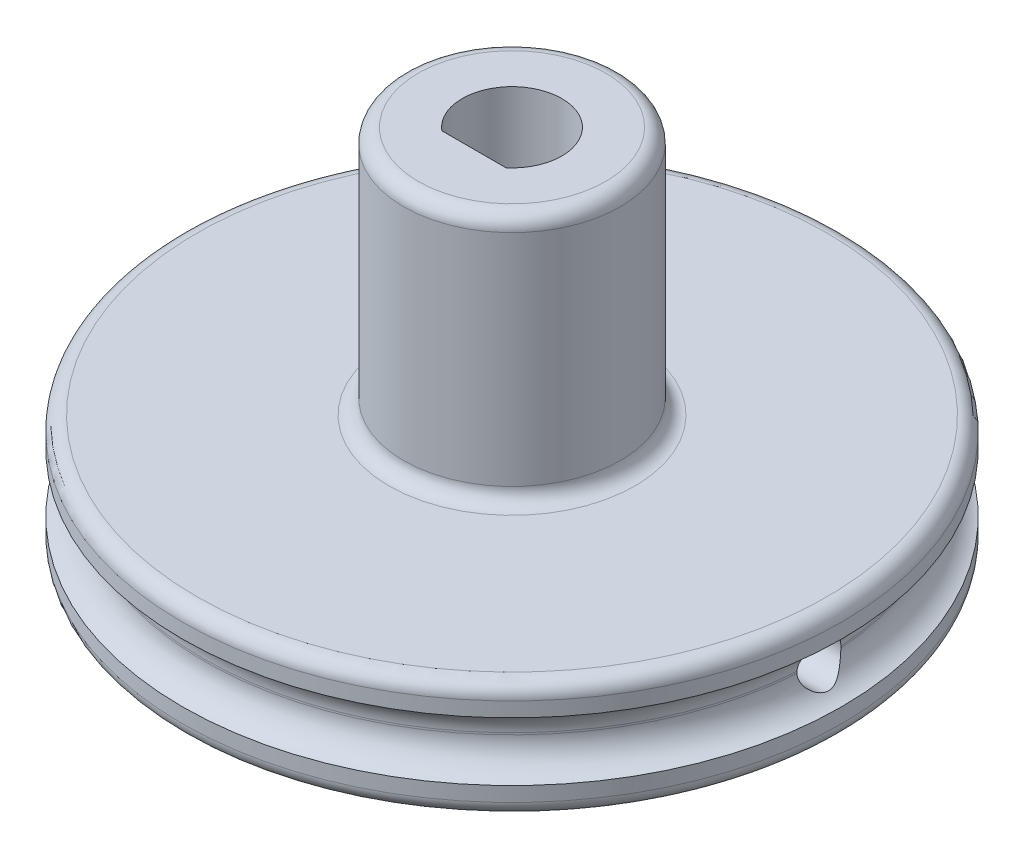
SolidWorks part; units mm, degrees
ref_plane "Front Plane" through (0, 0, 0) normal (0, 0, 1) x (1, 0, 0)
ref_plane "Top Plane" through (0, 0, 0) normal (0, 1, 0) x (1, 0, 0)
ref_plane "Right Plane" through (0, 0, 0) normal (1, 0, 0) x (0, 0, -1)
sketch "Sketch1" plane through (0, 0, 0) normal (0, 1, 0) x (1, 0, 0)
  line L0 (-1.0954, -1.3) -> (1.0954, -1.3)
  line L1 (0, -1.3) -> (0, -1.7)
  circle A0 centre (0, 0) radius 1.7
  circle A1 centre (0, 0) radius 11.25
  dimension "D1" = 3.4
  dimension "D2" = 22.5
  dimension "D3" = 0.4
extrude "Boss-Extrude1" add sketch "Sketch1" along normal blind 4 contours A1 A0 | L1 A0 L0 | L0 A0 L1 region at (-0.4181, 0, 1.4617) region at (0.4181, 0, 1.4617) region at (-10.9318, 0, 0)
sketch "Sketch2" plane through (0, 4, 0) normal (0, 1, 0) x (1, 0, 0)
  line L1 (1.7, 0) -> (3.7, 0) construction
  line L2 (-1.0954, -1.3) -> (1.0954, -1.3)
  circle A0 centre (0, 0) radius 3.7
  arc A1 (1.0954, -1.3) -> (-1.0954, -1.3) centre (0, 0) ccw construction
  arc A2 (-1.0954, -1.3) -> (1.0954, -1.3) centre (0, 0) cw
  dimension "D2" = 1.7
  dimension "D1" = 2
extrude "Boss-Extrude2" add sketch "Sketch2" along normal blind 8.5
sketch "Sketch3" plane through (0, 12.5, 0) normal (0, 1, 0) x (1, 0, 0)
  line L0 (0, 0) -> (0, -3.7) construction
  circle A0 centre (0, 0) radius 3.7 construction
sketch "Sketch4" plane through (0, 0, 0) normal (0, -1, 0) x (1, 0, 0)
  line L0 (0, 0) -> (0, 11.25) construction
  circle A0 centre (0, 0) radius 11.25 construction
ref_plane "Plane1" through (0, 0, 0) normal (1, 0, 0) x (0, 0, -1)
ref_plane "Plane2" through (12.5, 0, 0) normal (1, 0, 0) x (0, 0, -1)
sketch "Sketch5" plane through (12.5, 0, 0) normal (1, 0, 0) x (0, 0, -1)
  line L0 (0, 0) -> (0, 4) construction
  line L4 (11.25, 4) -> (-11.25, 4) construction
  circle A0 centre (0, 2) radius 0.75
  dimension "D1" = 1.5
sketch3d "3DSketch1"
  line L0 (12.5, 0, 0) -> (12.5, 4, 0) construction
  line L1 (12.5, 2, 0) -> (9.1368, 2, 0)
  line L3 (9.1368, 2, 0) -> (7.1368, 2, 0) construction
  line L4 (7.1368, 0, 0) -> (7.1368, -2.2816, 0)
  arc A0 (7.1368, 0, 0) -> (9.1368, 2, 0) centre (9.1368, 0, 0) ccw
  point P6 (7.1368, 2, 0)
  point P8 (9.1368, 0, -2)
  dimension "D1" = 2
sweep "Cut-Sweep1" cut path "3DSketch1" circular profile diameter 1.5 parameters "D3"=1.5
mirror "Mirror1" about plane through (0, 0, 0) normal (1, 0, 0) of "Cut-Sweep1"
ref_plane "Plane3" through (0, 2, 0) normal (0, 1, 0) x (1, 0, 0)
sketch "Sketch21" plane through (0, 2, 0) normal (0, 1, 0) x (1, 0, 0)
  circle A0 centre (0, 0) radius 12.5
  circle A1 centre (0, 0) radius 10.5
  dimension "D1" = 25
  dimension "D2" = 2
extrude "Cut-Extrude1" cut sketch "Sketch21" against normal mid plane 2
fillet "Fillet1" radius 1 2 edges at (0, 1, 10.5) (0, 3, 10.5)
fillet "Fillet2" radius 0.5 4 edges at (0, 4, 3.7) (0, 12.5, 3.7) (0, 0, 11.25) (0, 4, 11.25)
